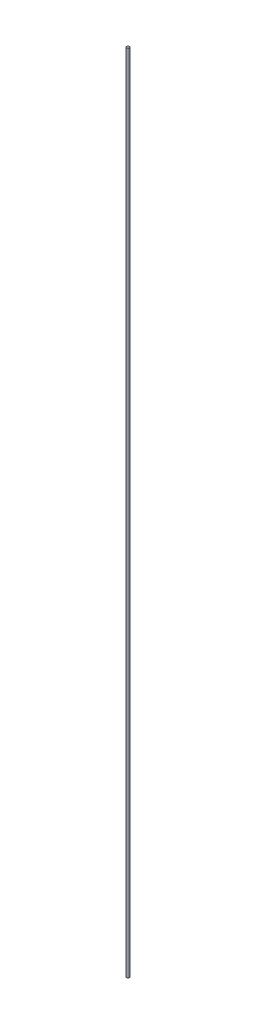
SolidWorks part; units mm, degrees
ref_plane "Ebene vorne" through (0, 0, 0) normal (0, 0, 1) x (1, 0, 0)
ref_plane "Ebene oben" through (0, 0, 0) normal (0, 1, 0) x (1, 0, 0)
ref_plane "Ebene rechts" through (0, 0, 0) normal (1, 0, 0) x (0, 0, -1)
sketch "Skizze1" plane through (0, 0, 0) normal (0, 1, 0) x (1, 0, 0)
  circle A0 centre (0, 0) radius 1
  dimension "D1" = 2
extrude "Aufsatz-Linear austragen1" add sketch "Skizze1" along normal blind 600
ref_axis "Achse1" through (0, -30, 0) along (0, 1, 0)
